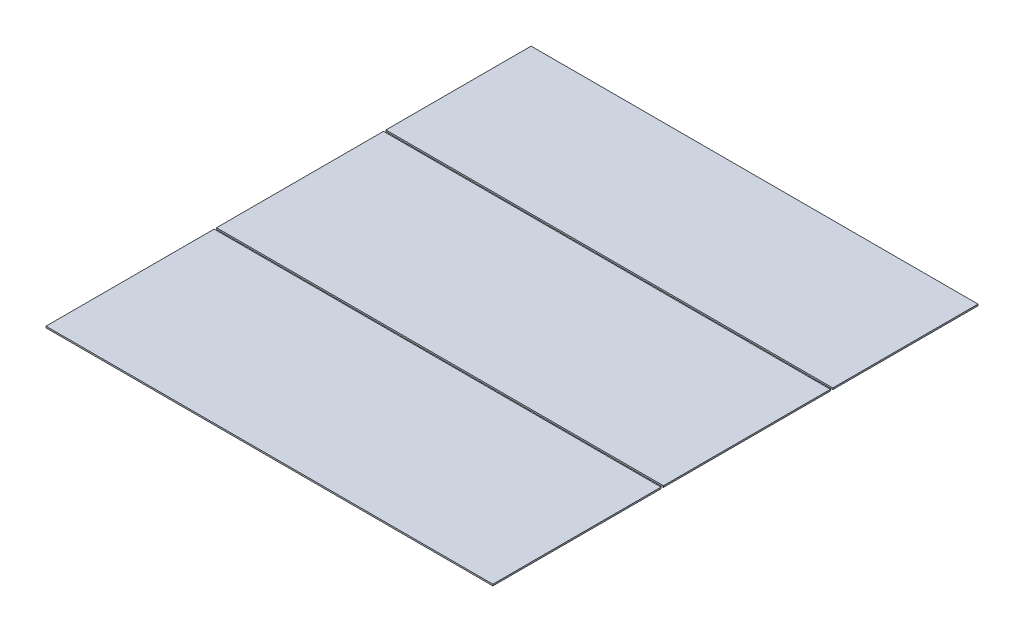
SolidWorks part; units mm, degrees
ref_plane "Front Plane" through (0, 0, 0) normal (0, 0, 1) x (1, 0, 0)
ref_plane "Top Plane" through (0, 0, 0) normal (0, 1, 0) x (1, 0, 0)
ref_plane "Right Plane" through (0, 0, 0) normal (1, 0, 0) x (0, 0, -1)
sketch "Sketch1" plane through (0, 0, 0) normal (0, 1, 0) x (1, 0, 0)
  line L1 (-736.6, 329.532) -> (736.6, 329.532)
  line L2 (-736.6, 329.532) -> (-736.6, 800.1)
  line L3 (-736.6, 800.1) -> (736.6, 800.1)
  line L4 (736.6, 329.532) -> (736.6, 800.1)
  line L5 (-736.6, 329.532) -> (736.6, 800.1) construction
  line L6 (-736.6, 800.1) -> (736.6, 329.532) construction
  line L11 (-736.6, -800.1) -> (736.6, -800.1)
  line L12 (-736.6, -800.1) -> (-736.6, -253.332)
  line L13 (-736.6, -253.332) -> (736.6, -253.332)
  line L14 (736.6, -800.1) -> (736.6, -253.332)
  line L23 (736.6, -233.332) -> (-736.6, -233.332)
  line L24 (736.6, -233.332) -> (736.6, 309.532)
  line L25 (736.6, 309.532) -> (-736.6, 309.532)
  line L26 (-736.6, -233.332) -> (-736.6, 309.532)
  point P0 (0, 0)
extrude "Boss-Extrude1" add sketch "Sketch1" along normal blind 2.5 and the other way blind 2.5
sketch "Sketch2" plane through (0, 0, 0) normal (0, 1, 0) x (1, 0, 0)
  line L5 (-736.6, 800.1) -> (736.6, 800.1)
  line L6 (-736.6, 800.1) -> (-736.6, 329.532)
  line L11 (-736.6, 329.532) -> (736.6, 329.532)
  line L12 (736.6, 800.1) -> (736.6, 329.532)
  line L13 (-736.6, -253.332) -> (736.6, -253.332)
  line L14 (-736.6, -253.332) -> (-736.6, -800.1)
  line L15 (-736.6, -800.1) -> (736.6, -800.1)
  line L16 (736.6, -253.332) -> (736.6, -800.1)
  line L17 (-742.6, 806.1) -> (742.6, 806.1)
  line L18 (-742.6, 806.1) -> (-742.6, 323.532)
  line L19 (-742.6, 323.532) -> (742.6, 323.532)
  line L20 (742.6, 806.1) -> (742.6, 323.532)
  line L21 (742.6, -806.1) -> (-742.6, -806.1)
  line L22 (742.6, -806.1) -> (742.6, -247.332)
  line L23 (742.6, -247.332) -> (-742.6, -247.332)
  line L24 (-742.6, -806.1) -> (-742.6, -247.332)
  line L25 (-736.6, 309.532) -> (736.6, 309.532)
  line L26 (-736.6, 309.532) -> (-736.6, -233.332)
  line L27 (-736.6, -233.332) -> (736.6, -233.332)
  line L28 (736.6, 309.532) -> (736.6, -233.332)
  line L29 (-742.6, 315.532) -> (742.6, 315.532)
  line L30 (-742.6, 315.532) -> (-742.6, -239.332)
  line L31 (-742.6, -239.332) -> (742.6, -239.332)
  line L32 (742.6, 315.532) -> (742.6, -239.332)
  dimension "D1" = 6
  dimension "D2" = 6
  dimension "D3" = 6
  dimension "D4" = 6
  dimension "D5" = 6
  dimension "D6" = 6
  dimension "D7" = 6
  dimension "D8" = 6
extrude "Boss-Extrude2" add sketch "Sketch2" along normal up to surface and the other way up to surface up to face at (0, 2.5, -564.816) other way up to face at (0, -2.5, -564.816)
